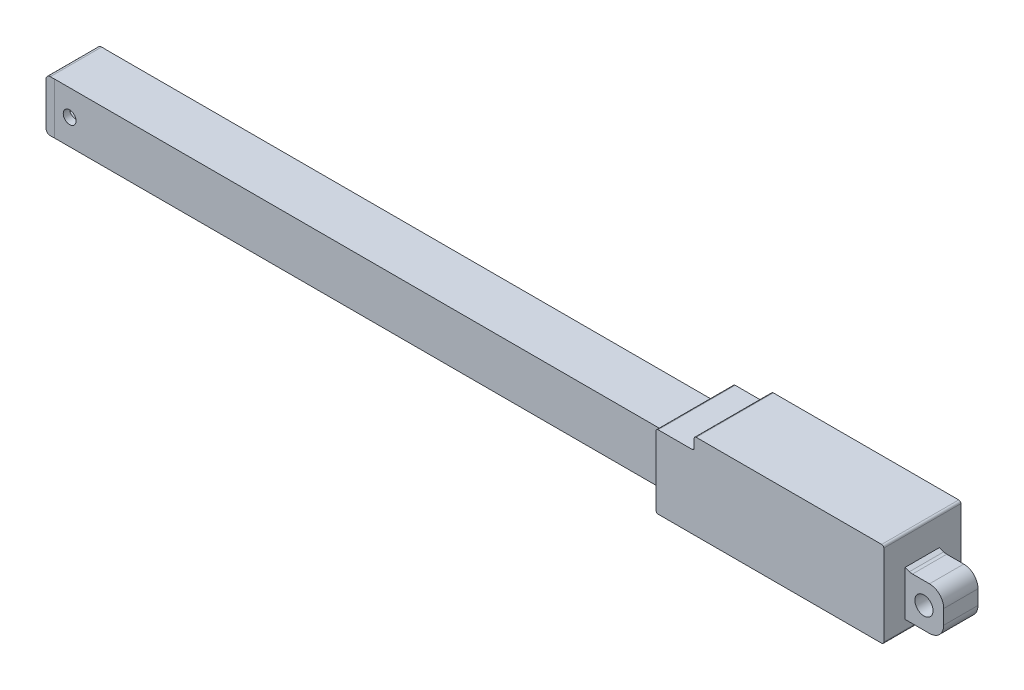
SolidWorks part; units mm, degrees
ref_plane "Front Plane" through (0, 0, 0) normal (0, 0, 1) x (1, 0, 0)
ref_plane "Top Plane" through (0, 0, 0) normal (0, 1, 0) x (1, 0, 0)
ref_plane "Right Plane" through (0, 0, 0) normal (1, 0, 0) x (0, 0, -1)
sketch "Sketch2" plane through (0, 0, 0) normal (0, 0, 1) x (1, 0, 0)
  line L0 (145.4775, 11.945) -> (145.4775, 14.0125)
  line L1 (1, 0) -> (145.4775, 0)
  line L2 (0, 1) -> (0, 10.945)
  line L3 (1, 11.945) -> (145.4775, 11.945)
  line L4 (145.4775, 0) -> (145.4775, 11.945)
  line L5 (145.4775, 0) -> (145.4775, -2.0675)
  line L6 (145.9775, -2.5675) -> (198.1775, -2.5675)
  line L7 (198.6775, 0) -> (198.6775, -2.0675)
  line L8 (198.1775, 17.4325) -> (154.8775, 17.4325)
  line L9 (154.3775, 16.9325) -> (154.3775, 15.0125)
  line L10 (153.8775, 14.5125) -> (145.9775, 14.5125)
  line L11 (198.6775, 0) -> (204.3439, 0)
  line L12 (207.6775, 3.3336) -> (207.6775, 6.7089)
  line L13 (204.3439, 10.0425) -> (200.3774, 10.0425)
  line L14 (199.6775, 10.169) -> (198.6775, 10.5425)
  line L15 (203.0525, 0) -> (203.0525, 10.0425) construction
  line L16 (2, 11.945) -> (2, 0)
  line L17 (198.6775, 10.5425) -> (198.6775, 16.9325)
  line L18 (2, 5.9725) -> (4, 5.9725) construction
  line L19 (0, 5.9725) -> (2, 5.9725) construction
  arc A0 (0, 10.945) -> (1, 11.945) centre (1, 10.945) cw
  arc A1 (1, 0) -> (0, 1) centre (1, 1) cw
  arc A2 (154.8775, 17.4325) -> (154.3775, 16.9325) centre (154.8775, 16.9325) ccw
  arc A3 (198.6775, 16.9325) -> (198.1775, 17.4325) centre (198.1775, 16.9325) ccw
  arc A4 (198.1775, -2.5675) -> (198.6775, -2.0675) centre (198.1775, -2.0675) ccw
  arc A5 (145.4775, -2.0675) -> (145.9775, -2.5675) centre (145.9775, -2.0675) ccw
  arc A6 (145.4775, 14.0125) -> (145.9775, 14.5125) centre (145.9775, 14.0125) cw
  arc A7 (154.3775, 15.0125) -> (153.8775, 14.5125) centre (153.8775, 15.0125) cw
  arc A8 (204.3439, 0) -> (207.6775, 3.3336) centre (204.3439, 3.3336) ccw
  arc A9 (207.6775, 6.7089) -> (204.3439, 10.0425) centre (204.3439, 6.7089) ccw
  circle A10 centre (203.0525, 5.0213) radius 2.125
  arc A11 (200.3774, 10.0425) -> (199.6775, 10.169) centre (200.3774, 12.0425) cw
  circle A12 centre (5.5, 5.9725) radius 1.5
  point P7 (0, 11.945)
  point P10 (0, 0)
  point P23 (191, -2.5)
  point P26 (145.4775, -2.5675)
  point P29 (145.4775, 14.5125)
  point P32 (154.3775, 14.5125)
  point P44 (203.0525, 5.0213)
  point P54 (4, 5.9725)
  point P57 (205.1775, 5.0213)
  dimension "D3" = 1
  dimension "D8" = 0.5
  dimension "D12" = 4.25
  dimension "D13" = 2
  dimension "D14" = 3
  dimension "D9" = 2.5
  dimension "D1" = 145.4775
  dimension "D2" = 11.945
  dimension "D4" = 53.2
  dimension "D5" = 17.08
  dimension "D6" = 20
  dimension "D7" = 44.3
  dimension "D10" = 10.0425
  dimension "D11" = 9
  dimension "D15" = 2
  dimension "D16" = 1
  dimension "D17" = 0.5
extrude "Boss-Extrude1" add sketch "Sketch2" along normal mid plane 18 contours L9 A7 L10 A6 L0 L4 L5 A5 L6 A4 A3 L8 A2 region at (174.5921, 7.0781, 0)
extrude "Boss-Extrude2" add sketch "Sketch2<3>" along normal mid plane 11.95 contours L3 L16 L1 L4 A12 region at (74.0214, 5.9725, 0)
sketch "Sketch2<3>" plane through (0, 0, 0) normal (0, 0, 1) x (1, 0, 0) same geometry as "Sketch2"
extrude "Boss-Extrude3" add sketch "Sketch2<4>" along normal mid plane 12 contours A1 L1 L16 L3 A0 L2 region at (1.0142, 5.9725, 0)
sketch "Sketch2<4>" plane through (0, 0, 0) normal (0, 0, 1) x (1, 0, 0) same geometry as "Sketch2"
sketch "Sketch7" plane through (0, 0, 0) normal (-1, 0, 0) x (0, 0, 1)
  line L0 (0, 1) -> (6, 5.9725) construction
  line L1 (6, 1) -> (-6, 1) construction
  line L2 (6, 1) -> (6, 10.945) construction
  line L3 (6, 5.9725) -> (0, 5.9725) construction
  circle A0 centre (0, 5.9725) radius 4.45
  dimension "D1" = 8.9
extrude "Cut-Extrude4" cut sketch "Sketch7" against normal blind 138
sketch "Sketch8" plane through (0, 0, 9) normal (0, 0, 1) x (1, 0, 0)
  line L0 (198.6775, 10.5425) -> (211.4521, 15.9059)
  line L1 (211.4521, 15.9059) -> (207.0125, -2.0597)
  line L2 (207.0125, -2.0597) -> (198.6775, 0)
  line L3 (198.6775, 0) -> (204.3439, 0) construction
  line L4 (198.6775, 0) -> (198.6775, 10.5425)
extrude "Cut-Extrude6" cut sketch "Sketch8" against normal mid plane 10
sketch "Sketch10" plane through (0, 0, -9) normal (0, 0, -1) x (-1, 0, 0)
  line L0 (-198.6775, 10.5425) -> (-218.6867, 39.1128)
  line L1 (-218.6867, 39.1128) -> (-201.4433, -35.5929)
  line L2 (-201.4433, -35.5929) -> (-198.6775, 0)
  line L3 (-198.6775, 0) -> (-198.6775, 10.5425)
extrude "Cut-Extrude7" cut sketch "Sketch10" against normal mid plane 10
